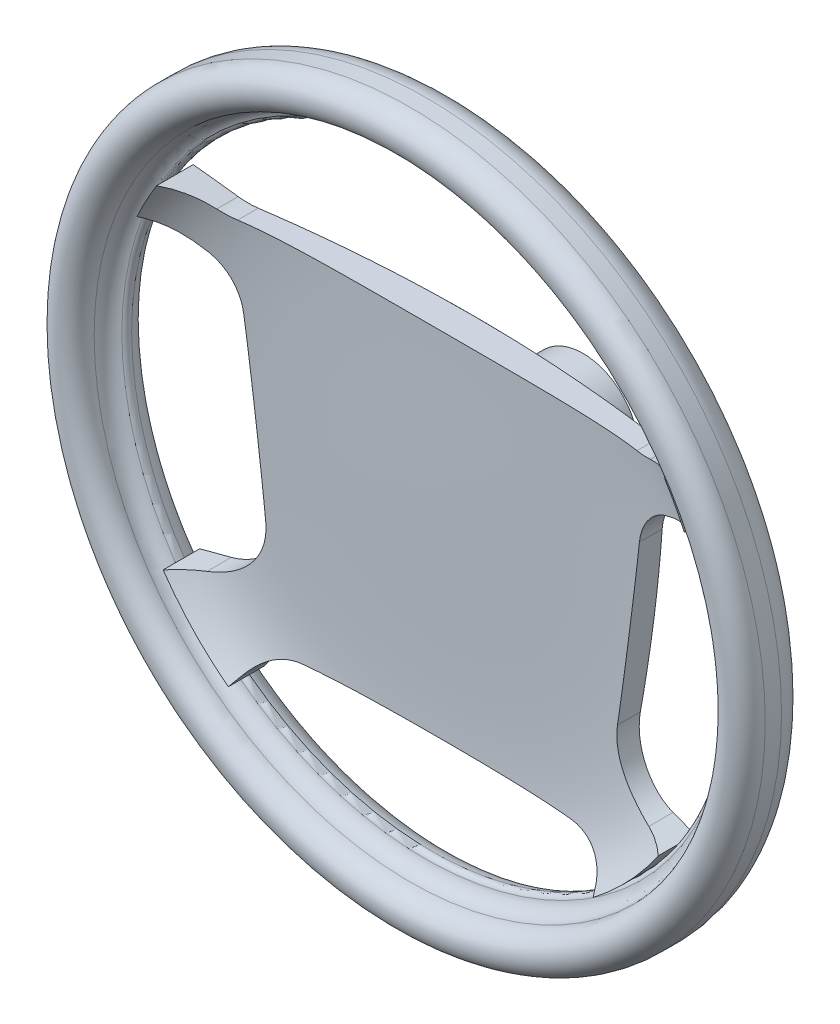
SolidWorks part; units mm, degrees
ref_plane "Front Plane" through (0, 0, 0) normal (0, 0, 1) x (1, 0, 0)
ref_plane "Top Plane" through (0, 0, 0) normal (0, 1, 0) x (1, 0, 0)
ref_plane "Right Plane" through (0, 0, 0) normal (1, 0, 0) x (0, 0, -1)
sketch "Sketch4" plane through (0, 0, 0) normal (0, 1, 0) x (1, 0, 0)
  line L0 (0, 62.4758) -> (0, -42.0515) construction
  line L1 (0, 17.4625) -> (146.05, 17.4625) construction
  line L2 (163.5125, 0) -> (0, 0) construction
  line L3 (173.0375, 17.4625) -> (173.0375, 9.525)
  arc A0 (146.3176, 20.1365) -> (173.0375, 17.4625) centre (159.5437, 17.4625) cw
  arc A1 (146.3176, 20.1365) -> (148.1388, 17.1827) centre (148.8072, 19.6332) ccw
  arc A3 (148.1388, 17.1827) -> (153.9875, 9.525) centre (146.05, 9.525) cw
  arc A4 (153.9875, 9.525) -> (173.0375, 9.525) centre (163.5125, 9.525) ccw
  dimension "D2" = 26.9875
  dimension "D3" = 2.54
  dimension "D4" = 19.05
  dimension "D1" = 292.1
revolve "Revolve2" add sketch "Sketch4" angle 360 about L0
sketch "Sketch6" plane through (0, 0, 0) normal (0, 0, 1) x (1, 0, 0)
  line L0 (0, 146.3176) -> (0, -146.2672) construction
  line L1 (-101.6, 70.1176) -> (101.6, 70.1176)
  line L2 (101.6, 70.1176) -> (123.825, 77.8555)
  line L3 (133.35, 60.0989) -> (98.211, 43.9739)
  line L4 (98.211, 43.9739) -> (82.4337, -77.7363)
  line L5 (82.4337, -77.7363) -> (120.65, -82.6903)
  line L6 (88.9, -116.1503) -> (79.375, -101.3324)
  line L7 (79.375, -101.3324) -> (-79.375, -101.3324)
  line L8 (98.211, 43.9739) -> (101.6, 70.1176) construction
  line L9 (79.375, -101.3324) -> (82.4337, -77.7363) construction
  line L10 (-79.375, -101.3324) -> (-82.4337, -77.7363) construction
  line L11 (-98.211, 43.9739) -> (-101.6, 70.1176) construction
  line L12 (-88.9, -116.1503) -> (-79.375, -101.3324)
  line L13 (-82.4337, -77.7363) -> (-120.65, -82.6903)
  line L14 (-98.211, 43.9739) -> (-82.4337, -77.7363)
  line L15 (-133.35, 60.0989) -> (-98.211, 43.9739)
  line L16 (-101.6, 70.1176) -> (-123.825, 77.8555)
  circle A0 centre (0, 0) radius 146.3176 construction
  circle A1 centre (0, 0) radius 146.2672 construction
  arc A2 (-120.65, -82.6903) -> (0, 146.2672) centre (0, 0) ccw
  arc A3 (133.35, 60.0989) -> (123.825, 77.8555) centre (0, 0) ccw
  arc A4 (88.9, -116.1503) -> (120.65, -82.6903) centre (0, 0) ccw
  arc A5 (-88.9, -116.1503) -> (-120.65, -82.6903) centre (0, 0) cw
  arc A6 (-133.35, 60.0989) -> (-123.825, 77.8555) centre (0, 0) cw
  arc A7 (-123.825, 77.8555) -> (-133.35, 60.0989) centre (0, 0) ccw
  point P17 (0, 70.1176)
  point P18 (0, -101.3324)
  dimension "D1" = 203.2
  dimension "D2" = 158.75
  dimension "D3" = 171.45
  dimension "D4" = 177.8
  dimension "D5" = 241.3
  dimension "D6" = 266.7
  dimension "D7" = 247.65
  dimension "D8" = 76.2
extrude "Boss-Extrude1" add sketch "Sketch6" against normal blind 50.8 separate body contours L3 A2 L2 L1 L16 L15 L14 L13 L12 L7 L6 L5 L4 region at (0, -13.5224, 0)
sketch "Sketch7" plane through (0, 0, 0) normal (0, 1, 0) x (1, 0, 0)
  line L0 (0, 0) -> (0, 25.4)
  line L1 (0, 0) -> (154.1091, 0)
  line L2 (42.568, 25.4) -> (-52.6095, 25.4) construction
  line L3 (-101.6, 0) -> (101.6, 0) construction
  line L4 (0, 50.8) -> (146.3176, 50.8)
  line L5 (-101.6, 50.8) -> (101.6, 50.8) construction
  line L7 (0, 50.8) -> (0, 43.4702)
  line L8 (58.7407, 43.4702) -> (-58.7407, 43.4702) construction
  line L10 (146.3176, 50.8) -> (146.3176, 27.588)
  spline S0 degree 3 poles (0, 25.4) (118.0264, 25.4) (133.9378, 29.3617) (154.1091, 0) knots 0 0 0 0 1 1 1 1
  spline S1 degree 2 poles (0, 43.4702) (73.4259, 43.4702) (146.3176, 27.588) knots 0 0 0 1 1 1
  spline S2 degree 2 poles (146.3176, 27.588) (22.5277, 50.8) (0, 50.8) knots 0 0 0 1 1 1 construction
  point P13 (146.3176, 20.1365)
  dimension "D1" = 25.4
revolve "Cut-Revolve3" cut sketch "Sketch7" angle 360 about L0 region at (70.169, 0, -12.0762) region at (88.4996, 0, -43.605)
sketch "Sketch8" plane through (0, 0, 0) normal (1, 0, 0) x (0, -1, 0)
  line L0 (0, 39.8368) -> (0, 77.9368)
  line L1 (-26.9875, 77.9368) -> (-26.9875, 93.8118)
  line L2 (-26.9875, 77.9368) -> (-70.1176, 39.8368)
  line L3 (-70.1176, 39.8368) -> (0, 39.8368)
  line L4 (0, 0) -> (0, 39.8368) construction
  line L5 (-70.1176, 39.8368) -> (-70.1176, 32.178) construction
  line L6 (-26.9875, 93.8118) -> (-23.8125, 93.8118)
  line L7 (-23.8125, 93.8118) -> (-23.8125, 77.9368)
  line L8 (-23.8125, 77.9368) -> (0, 77.9368)
  dimension "D1" = 3.175
  dimension "D2" = 38.1
  dimension "D3" = 53.975
  dimension "D4" = 15.875
revolve "Revolve3" add sketch "Sketch8" angle 360 about L4
sketch "Sketch9" plane through (0, 0, -77.9368) normal (0, 0, -1) x (-1, 0, 0)
  line L1 (-3.175, 3.175) -> (3.175, 3.175)
  line L2 (-3.175, 3.175) -> (-3.175, -3.175)
  line L3 (-3.175, -3.175) -> (3.175, -3.175)
  line L4 (3.175, 3.175) -> (3.175, -3.175)
  line L5 (-3.175, 3.175) -> (3.175, -3.175) construction
  line L6 (-3.175, -3.175) -> (3.175, 3.175) construction
  point P0 (0, 0)
  dimension "D1" = 6.35
fillet "Fillet1" radius 6.35 1 edges at (70.1176, 0, -39.8368)
fillet "Fillet2" radius 25.4 8 edges at (79.375, -101.3324, -25.8905) (82.4337, -77.7363, -28.8639) (-79.375, -101.3324, -25.8905) (-82.4337, -77.7363, -28.8639) (98.211, 43.9739, -29.6269) (101.6, 70.1176, -27.1075) (-101.6, 70.1176, -27.1075) (-98.211, 43.9739, -29.6269)
extrude "Cut-Extrude1" cut sketch "Sketch9" against normal blind 2.54 contours L1 L4 L3 L2
